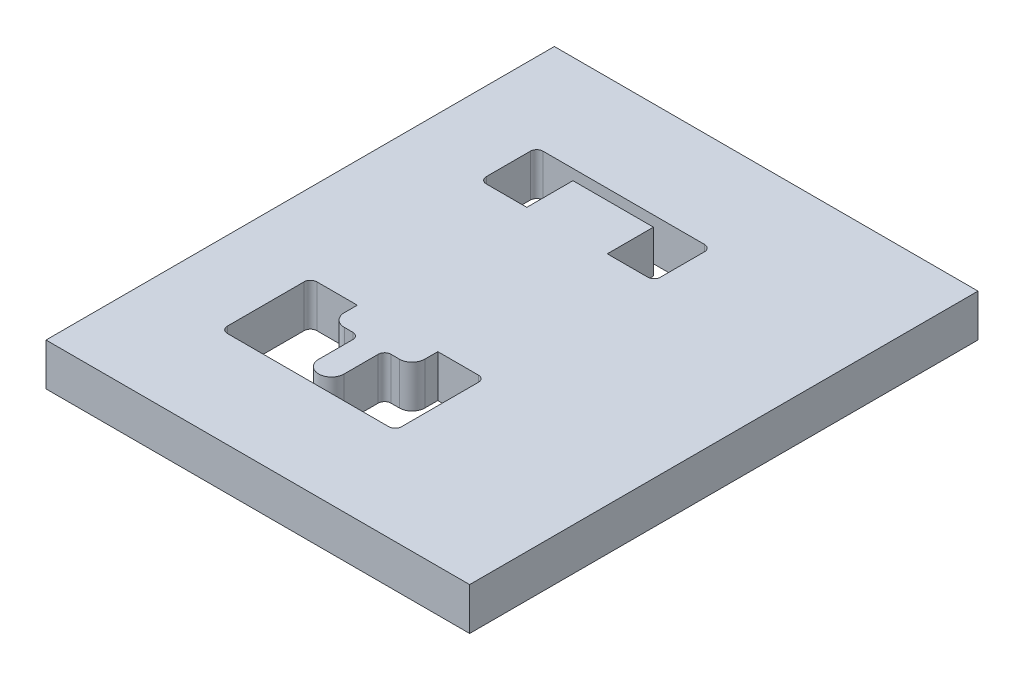
SolidWorks part; units mm, degrees
material "Plain Carbon Steel"
ref_plane "Front Plane" through (0, 0, 0) normal (0, 0, 1) x (1, 0, 0)
ref_plane "Top Plane" through (0, 0, 0) normal (0, 1, 0) x (1, 0, 0)
ref_plane "Right Plane" through (0, 0, 0) normal (1, 0, 0) x (0, 0, -1)
sketch "Sketch1" plane through (0, 0, 0) normal (0, 1, 0) x (1, 0, 0)
  line L1 (-100, -120) -> (100, -120)
  line L2 (-100, -120) -> (-100, 120)
  line L3 (-100, 120) -> (100, 120)
  line L4 (100, -120) -> (100, 120)
  line L5 (-100, -120) -> (100, 120) construction
  line L6 (-100, 120) -> (100, -120) construction
  point P0 (0, 0)
  dimension "D1" = 240
  dimension "D2" = 200
extrude "Boss-Extrude1" add sketch "Sketch1" against normal blind 20
sketch "Sketch5" plane through (0, 0, 0) normal (0, 1, 0) x (1, 0, 0)
  line L1 (8.38, -74.53) -> (-62.87, -74.53) construction
  line L2 (-62.87, -32.27) -> (-62.87, -74.53) construction
  line L3 (-62.87, -32.27) -> (-40.75, -32.27) construction
  line L4 (-40.75, -32.27) -> (-40.75, -38.4) construction
  line L5 (-34.75, -44.4) -> (-30.75, -44.4) construction
  line L6 (-27.75, -47.4) -> (-27.75, -63.53) construction
  line L7 (-15.75, -63.53) -> (-15.75, -47.4) construction
  line L8 (-12.75, -44.4) -> (-8.75, -44.4) construction
  line L9 (-2.75, -38.4) -> (-2.75, -32.27) construction
  line L10 (-2.75, -32.27) -> (8.38, -32.27) construction
  line L11 (-62.87, -35.27) -> (-62.87, -71.53)
  line L12 (16.37, -74.53) -> (-59.87, -74.53)
  line L14 (-2.75, -32.27) -> (16.37, -32.27)
  line L15 (-2.75, -38.4) -> (-2.75, -32.27)
  line L16 (-12.75, -44.4) -> (-8.75, -44.4)
  line L17 (-15.75, -63.53) -> (-15.75, -47.4)
  line L18 (-27.75, -47.4) -> (-27.75, -63.53)
  line L19 (-34.75, -44.4) -> (-30.75, -44.4)
  line L20 (-40.75, -32.27) -> (-40.75, -38.4)
  line L21 (-59.87, -32.27) -> (-40.75, -32.27)
  line L23 (-21.75, -63.53) -> (-21.75, -74.53) construction
  line L25 (19.37, -35.27) -> (19.37, -71.53)
  arc A0 (-40.75, -38.4) -> (-34.75, -44.4) centre (-34.75, -38.4) ccw construction
  arc A1 (-27.75, -47.4) -> (-30.75, -44.4) centre (-30.75, -47.4) ccw construction
  arc A2 (-27.75, -63.53) -> (-15.75, -63.53) centre (-21.75, -63.53) ccw construction
  arc A3 (-12.75, -44.4) -> (-15.75, -47.4) centre (-12.75, -47.4) ccw construction
  arc A4 (-8.75, -44.4) -> (-2.75, -38.4) centre (-8.75, -38.4) ccw construction
  arc A5 (-8.75, -44.4) -> (-2.75, -38.4) centre (-8.75, -38.4) ccw
  arc A6 (-12.75, -44.4) -> (-15.75, -47.4) centre (-12.75, -47.4) ccw
  arc A7 (-27.75, -63.53) -> (-15.75, -63.53) centre (-21.75, -63.53) ccw
  arc A8 (-27.75, -47.4) -> (-30.75, -44.4) centre (-30.75, -47.4) ccw
  arc A9 (-40.75, -38.4) -> (-34.75, -44.4) centre (-34.75, -38.4) ccw
  arc A10 (19.37, -71.53) -> (16.37, -74.53) centre (16.37, -71.53) cw
  arc A11 (19.37, -35.27) -> (16.37, -32.27) centre (16.37, -35.27) ccw
  arc A12 (-62.87, -35.27) -> (-59.87, -32.27) centre (-59.87, -35.27) cw
  arc A13 (-62.87, -71.53) -> (-59.87, -74.53) centre (-59.87, -71.53) ccw
  dimension "D1" = 3
extrude "Cut-Extrude3" cut sketch "Sketch5" against normal up to next
sketch "Sketch6" plane through (0, 0, 0) normal (0, 1, 0) x (1, 0, 0)
  line L0 (-62.87, 47.73) -> (-62.87, 74.53) construction
  line L1 (-40.75, 47.73) -> (-62.87, 47.73) construction
  line L2 (-40.75, 69.53) -> (-40.75, 47.73) construction
  line L3 (-2.75, 69.53) -> (-40.75, 69.53) construction
  line L4 (-2.75, 47.73) -> (-2.75, 69.53) construction
  line L5 (8.38, 47.73) -> (-2.75, 47.73) construction
  line L7 (-62.87, 74.53) -> (8.38, 74.53) construction
  line L8 (-62.87, 50.73) -> (-62.87, 71.53)
  line L9 (-40.75, 47.73) -> (-59.87, 47.73)
  line L10 (-40.75, 69.53) -> (-40.75, 47.73)
  line L11 (-2.75, 69.53) -> (-40.75, 69.53)
  line L12 (-2.75, 47.73) -> (-2.75, 69.53)
  line L13 (16.37, 47.73) -> (-2.75, 47.73)
  line L15 (-59.87, 74.53) -> (16.37, 74.53)
  line L16 (-21.75, 69.53) -> (-21.75, 47.73) construction
  line L17 (19.37, 71.53) -> (19.37, 50.73)
  arc A0 (19.37, 71.53) -> (16.37, 74.53) centre (16.37, 71.53) ccw
  arc A1 (19.37, 50.73) -> (16.37, 47.73) centre (16.37, 50.73) cw
  arc A2 (-62.87, 50.73) -> (-59.87, 47.73) centre (-59.87, 50.73) ccw
  arc A3 (-62.87, 71.53) -> (-59.87, 74.53) centre (-59.87, 71.53) cw
  dimension "D1" = 3
extrude "Cut-Extrude4" cut sketch "Sketch6" against normal up to next
